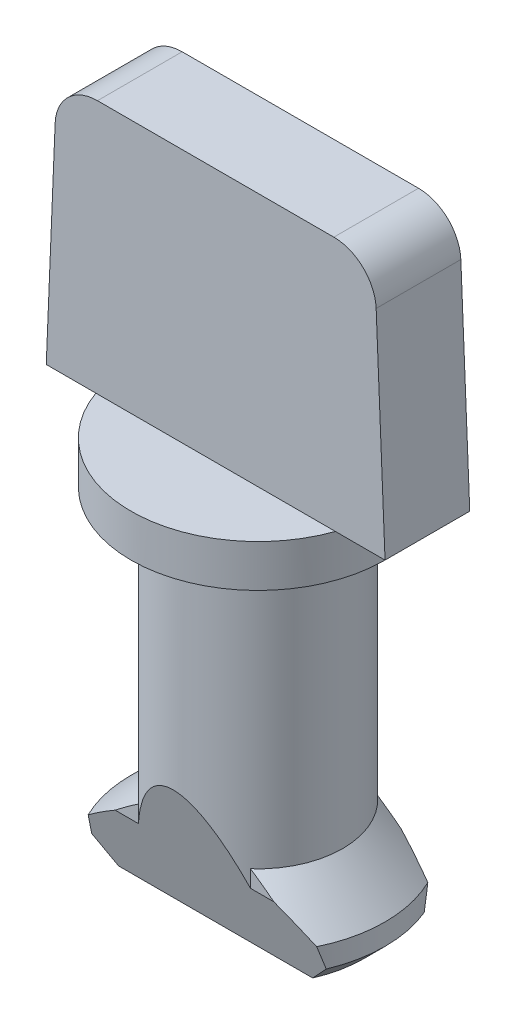
SolidWorks part; units mm, degrees
ref_plane "前视基准面" through (0, 0, 0) normal (0, 0, 1) x (1, 0, 0)
ref_plane "上视基准面" through (0, 0, 0) normal (0, 1, 0) x (1, 0, 0)
ref_plane "右视基准面" through (0, 0, 0) normal (1, 0, 0) x (0, 0, -1)
sketch "草图1" plane through (0, 0, 0) normal (0, 1, 0) x (1, 0, 0)
  circle A0 centre (0, 0) radius 3
extrude "凸台-拉伸1" add sketch "草图1" along normal blind 1
sketch "草图2" plane through (0, 0, 0) normal (0, 0, 1) x (1, 0, 0)
  line L0 (-3.75, 7) -> (3.75, 7)
  line L1 (-4, 1) -> (4, 1)
  line L2 (-3.75, 7) -> (-4, 1)
  line L3 (3.75, 7) -> (4, 1)
extrude "凸台-拉伸2" add sketch "草图2" along normal blind 1 and the other way blind 1
fillet "圆角1" radius 1 2 edges at (-3.75, 7, 0) (3.75, 7, 0)
sketch "草图3" plane through (0, 0, 0) normal (0, -1, 0) x (-1, 0, 0)
  circle A0 centre (0, 0) radius 2
extrude "凸台-拉伸3" add sketch "草图3" along normal blind 8.4
sketch "草图4" plane through (0, -8.4, 0) normal (0, -1, 0) x (-1, 0, 0)
  line L1 (2.5981, -1.5) -> (-2.5981, -1.5)
  line L3 (2.5981, 1.5) -> (-2.5981, 1.5)
  arc A0 (2.5981, -1.5) -> (2.5981, 1.5) centre (0, 0) ccw
  arc A1 (-2.5981, 1.5) -> (-2.5981, -1.5) centre (0, 0) ccw
extrude "凸台-拉伸4" add sketch "草图4" against normal blind 2
chamfer "倒角1" distance 0.5 angle 45 2 edges at (3, -8.4, 0) (-3, -8.4, 0)
chamfer "倒角2" distance 1 angle 45 2 edges at (3, -6.4, 0) (-3, -6.4, 0)
sketch "草图5" plane through (0, 0, 0) normal (1, 0, 0) x (0, 0, -1)
  line L0 (0, -6.4154) -> (0, -4.8208) construction
  line L1 (-1.5, -8.4) -> (1.5, -8.4) construction
  line L2 (2, -5.2) -> (1, -8.4)
  line L3 (-2, 0) -> (-2, -8.4) construction
  line L4 (-2, -5.2) -> (-2, -8.4)
  line L5 (-2, -8.4) -> (-1, -8.4)
  line L6 (-2, -5.2) -> (-1, -8.4)
  line L7 (2, -8.4) -> (1, -8.4)
  line L8 (2, -5.2) -> (2, -8.4)
extrude "切除-拉伸1" cut sketch "草图5" against normal up to next and the other way up to next
